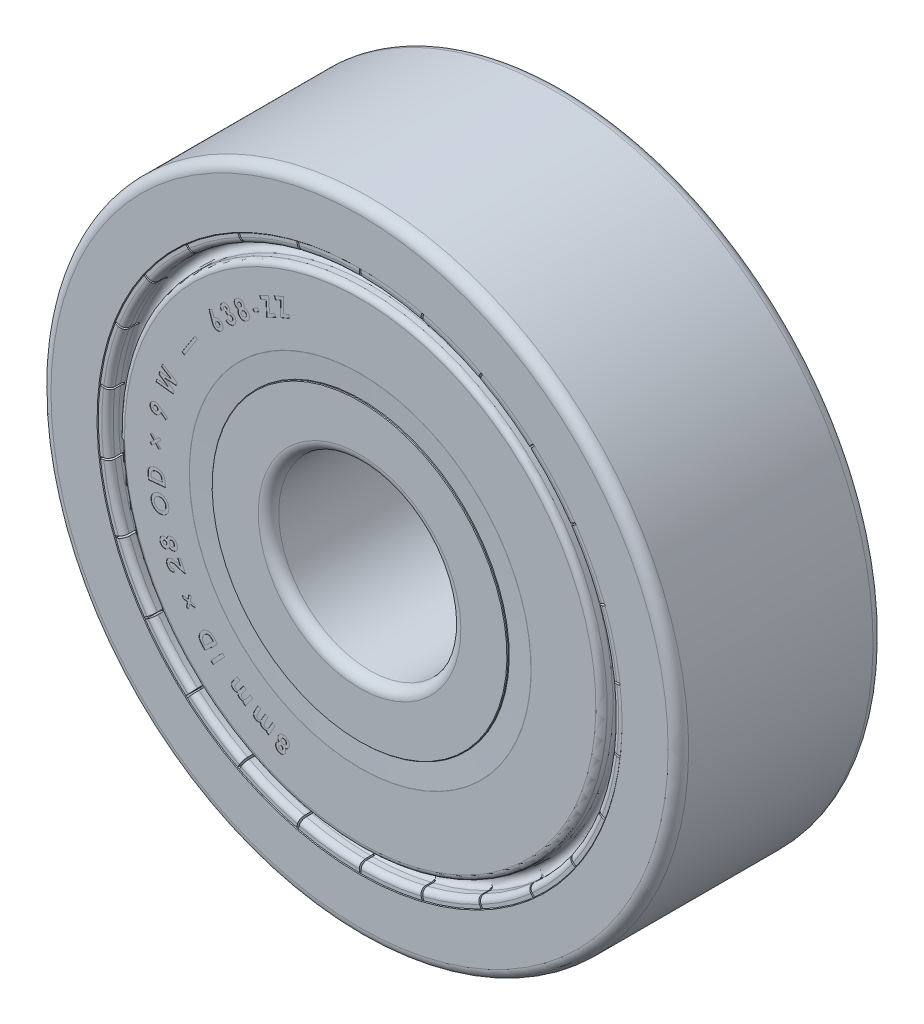
SolidWorks part; units mm, degrees
material "AISI 316 Annealed Stainless Steel Bar (SS)"
ref_plane "Front" through (0, 0, 0) normal (0, 0, 1) x (1, 0, 0)
ref_plane "Top" through (0, 0, 0) normal (0, 1, 0) x (1, 0, 0)
ref_plane "Right" through (0, 0, 0) normal (1, 0, 0) x (0, 0, -1)
sketch "LAYOUT R" plane through (0, 0, 0) normal (1, 0, 0) x (0, 0, -1)
  line L0 (-4.05, 4) -> (4.05, 4)
  line L1 (4.5, -14) -> (-4.5, -14) construction
  line L2 (4.5, -14) -> (4.5, 2.5781) construction
  line L3 (4.05, 14) -> (-4.05, 14)
  line L4 (-4.5, -14) -> (-4.5, 13.55) construction
  line L6 (2.6982, 0) -> (-2.6982, 0) construction
  line L7 (-4.472, 6.5) -> (4.472, 6.5)
  line L8 (-4.472, 11.5) -> (4.472, 11.5)
  line L11 (-8.89, 0) -> (8.89, 0) construction
  line L12 (-4.5, 13.55) -> (-4.5, 11.528)
  line L13 (4.5, 13.55) -> (4.5, 11.528)
  line L16 (-4.5, 6.472) -> (-4.5, 4.45)
  line L17 (4.5, 6.472) -> (4.5, 4.45)
  line L30 (-4.472, 11.5) -> (-4.472, 6.5) construction
  line L31 (4.472, 11.5) -> (4.472, 6.5) construction
  line L32 (-4.472, 7.5) -> (4.472, 7.5) construction
  line L33 (-4.4718, 7.5) -> (-4.4281, 6.5)
  line L34 (4.4718, 7.5) -> (4.4281, 6.5)
  line L35 (-4.472, 11.1) -> (4.472, 11.1) construction
  line L38 (-4.5, 11.528) -> (4.5, 11.528) construction
  line L39 (-4.472, 11.5) -> (-4.472, 11.35)
  line L40 (-4.222, 11.1) -> (-3.972, 11.1)
  line L41 (-4.472, 7.5109) -> (-4.472, 10.35)
  line L42 (-4.222, 10.6) -> (-3.972, 10.6)
  line L43 (4.472, 7.5109) -> (4.472, 10.35)
  line L44 (4.222, 10.6) -> (3.972, 10.6)
  line L45 (4.222, 11.1) -> (3.972, 11.1)
  line L46 (-4.472, 10.6) -> (4.472, 10.6) construction
  line L50 (-1.3199, 10.5) -> (1.3199, 10.5) construction
  line L53 (4.472, 6.5) -> (4.5, 6.472)
  line L54 (-4.472, 6.5) -> (-4.5, 6.472)
  line L56 (-4.5, 6.472) -> (4.5, 6.472) construction
  line L57 (4.5, 11.528) -> (4.472, 11.5) construction
  line L58 (4.5, 11.528) -> (4.472, 11.5)
  line L60 (-4.5, 11.528) -> (-4.472, 11.5) construction
  line L61 (-4.5, 11.528) -> (-4.472, 11.5)
  line L64 (-3.972, 10.6) -> (-3.972, 11.1) construction
  line L65 (3.972, 10.6) -> (3.972, 11.1) construction
  line L66 (4.472, 11.5) -> (4.472, 11.35)
  arc A2 (-4.222, 10.6) -> (-4.472, 10.35) centre (-4.222, 10.35) ccw
  arc A3 (4.472, 10.35) -> (4.222, 10.6) centre (4.222, 10.35) ccw
  arc A4 (4.4718, 7.5) -> (4.472, 7.5109) centre (4.222, 7.5109) ccw
  arc A5 (-4.472, 7.5109) -> (-4.4718, 7.5) centre (-4.222, 7.5109) ccw
  arc A6 (-3.972, 10.6) -> (-3.972, 11.1) centre (-3.972, 10.85) ccw
  arc A7 (3.972, 11.1) -> (3.972, 10.6) centre (3.972, 10.85) ccw
  arc A8 (-4.05, 14) -> (-4.5, 13.55) centre (-4.05, 13.55) ccw
  arc A9 (-4.5, 4.45) -> (-4.05, 4) centre (-4.05, 4.45) ccw
  arc A10 (4.05, 4) -> (4.5, 4.45) centre (4.05, 4.45) ccw
  arc A11 (-4.472, 11.35) -> (-4.222, 11.1) centre (-4.222, 11.35) ccw
  arc A12 (4.222, 11.1) -> (4.472, 11.35) centre (4.222, 11.35) ccw
  arc A13 (4.5, 13.55) -> (4.05, 14) centre (4.05, 13.55) ccw
  point P0 (0, 0)
  point P7 (-4.05, 14)
  point P8 (-4.222, 11.1)
  point P15 (0, 0)
  point P29 (-4.472, 11.35)
  point P38 (-4.4718, 7.5)
  point P54 (-4.472, 10.35)
  point P55 (-4.222, 10.6)
  point P56 (-4.472, 10.35)
  point P58 (-4.472, 7.5109)
  point P59 (-4.4718, 7.5)
  point P60 (4.222, 10.6)
  point P62 (4.472, 10.35)
  point P63 (4.472, 7.5109)
  point P64 (4.4718, 7.5)
  point P71 (-4.5, 13.55)
  point P72 (-4.5, 4.45)
  point P73 (-4.05, 4)
  point P74 (4.05, 4)
  point P75 (4.5, 4.45)
  point P80 (4.05, 14)
  point P81 (4.222, 11.1)
  point P88 (4.472, 11.35)
  point P91 (4.5, 13.55)
  dimension "D21" = 0.5
  dimension "D33" = 0.45
  dimension "D3" = 4
  dimension "D4" = 6.5
  dimension "D5" = 11.5
  dimension "D24" = 9
  dimension "D6" = 8.972
  dimension "D7" = 8.972
  dimension "D11" = 1
  dimension "D12" = 2.5
  dimension "D13" = 2.5
  dimension "D14" = 0.4
  dimension "D17" = 0.028
  dimension "D18" = 0.5
  dimension "D19" = 0.5
  dimension "D20" = 0.5
  dimension "D15" = 1
  dimension "D23" = 45
  dimension "D25" = 45
  dimension "D27" = 0.028
  dimension "D28" = 14
  dimension "D29" = 9
  dimension "D30" = 28
  dimension "D8" = 4.5
  dimension "D31" = 45
  dimension "D32" = 45
sketch "Sketch R, INNER BODY" plane through (0, 0, 0) normal (1, 0, 0) x (0, 0, -1)
  line L1 (-4.472, 6.5) -> (-4.5, 6.472) construction
  line L3 (-4.5, 6.472) -> (-4.5, 4.45) construction
  line L12 (-8.89, 0) -> (8.89, 0) construction
  line L13 (-8.89, 0) -> (8.89, 0) construction
  line L14 (-4.05, 4) -> (4.05, 4) construction
  line L15 (4.5, 6.472) -> (4.5, 4.45) construction
  line L16 (4.472, 6.5) -> (4.5, 6.472) construction
  line L17 (-4.472, 6.5) -> (4.472, 6.5) construction
  line L18 (-4.472, 6.5) -> (-4.5, 6.472)
  line L19 (-4.5, 6.472) -> (-4.5, 4.45)
  line L20 (-4.05, 4) -> (4.05, 4)
  line L21 (4.5, 6.472) -> (4.5, 4.45)
  line L22 (4.472, 6.5) -> (4.5, 6.472)
  line L23 (-4.472, 6.5) -> (4.472, 6.5)
  arc A0 (-4.5, 4.45) -> (-4.05, 4) centre (-4.05, 4.45) ccw construction
  arc A1 (4.05, 4) -> (4.5, 4.45) centre (4.05, 4.45) ccw construction
  arc A2 (-4.5, 4.45) -> (-4.05, 4) centre (-4.05, 4.45) ccw
  arc A3 (4.05, 4) -> (4.5, 4.45) centre (4.05, 4.45) ccw
sketch "Sketch R, OUTER BODY" plane through (0, 0, 0) normal (1, 0, 0) x (0, 0, -1)
  line L8 (-8.89, 0) -> (8.89, 0) construction
  line L9 (-8.89, 0) -> (8.89, 0) construction
  line L31 (-4.5, 13.55) -> (-4.5, 11.528) construction
  line L84 (-4.5, 11.528) -> (-4.472, 11.5) construction
  line L85 (-4.472, 11.5) -> (4.472, 11.5) construction
  line L86 (4.5, 11.528) -> (4.472, 11.5) construction
  line L87 (4.5, 13.55) -> (4.5, 11.528) construction
  line L88 (4.05, 14) -> (-4.05, 14) construction
  line L89 (-4.5, 13.55) -> (-4.5, 11.528)
  line L90 (-4.5, 11.528) -> (-4.472, 11.5)
  line L91 (-4.472, 11.5) -> (4.472, 11.5)
  line L92 (4.5, 11.528) -> (4.472, 11.5)
  line L93 (4.5, 13.55) -> (4.5, 11.528)
  line L94 (4.05, 14) -> (-4.05, 14)
  arc A6 (4.5, 13.55) -> (4.05, 14) centre (4.05, 13.55) ccw construction
  arc A7 (-4.05, 14) -> (-4.5, 13.55) centre (-4.05, 13.55) ccw construction
  arc A8 (4.5, 13.55) -> (4.05, 14) centre (4.05, 13.55) ccw
  arc A9 (-4.05, 14) -> (-4.5, 13.55) centre (-4.05, 13.55) ccw
sketch "Sketch R, SHIELD FACES" plane through (0, 0, 0) normal (1, 0, 0) x (0, 0, -1)
  line L0 (-8.89, 0) -> (8.89, 0) construction
  line L1 (-8.89, 0) -> (8.89, 0) construction
  line L29 (-4.472, 11.5) -> (-4.472, 11.35) construction
  line L32 (-4.222, 11.1) -> (-3.972, 11.1) construction
  line L34 (-4.222, 10.6) -> (-3.972, 10.6) construction
  line L36 (-4.472, 7.5109) -> (-4.472, 10.35) construction
  line L38 (-4.4718, 7.5) -> (-4.4281, 6.5) construction
  line L39 (-4.472, 6.5) -> (4.472, 6.5) construction
  line L40 (4.4718, 7.5) -> (4.4281, 6.5) construction
  line L43 (4.472, 7.5109) -> (4.472, 10.35) construction
  line L79 (4.222, 10.6) -> (3.972, 10.6) construction
  line L80 (4.222, 11.1) -> (3.972, 11.1) construction
  line L81 (4.472, 11.5) -> (4.472, 11.35) construction
  line L82 (-4.472, 11.5) -> (4.472, 11.5) construction
  line L83 (-4.472, 11.5) -> (-4.472, 11.35)
  line L84 (-4.222, 11.1) -> (-3.972, 11.1)
  line L85 (-4.222, 10.6) -> (-3.972, 10.6)
  line L86 (-4.472, 7.5109) -> (-4.472, 10.35)
  line L87 (-4.4718, 7.5) -> (-4.4281, 6.5)
  line L88 (-4.4281, 6.5) -> (4.4281, 6.5)
  line L89 (4.4718, 7.5) -> (4.4281, 6.5)
  line L90 (4.472, 7.5109) -> (4.472, 10.35)
  line L91 (4.222, 10.6) -> (3.972, 10.6)
  line L92 (4.222, 11.1) -> (3.972, 11.1)
  line L93 (4.472, 11.5) -> (4.472, 11.35)
  line L94 (-4.472, 11.5) -> (4.472, 11.5)
  arc A28 (-4.472, 11.35) -> (-4.222, 11.1) centre (-4.222, 11.35) ccw construction
  arc A29 (-3.972, 10.6) -> (-3.972, 11.1) centre (-3.972, 10.85) ccw construction
  arc A30 (-4.222, 10.6) -> (-4.472, 10.35) centre (-4.222, 10.35) ccw construction
  arc A31 (4.472, 10.35) -> (4.222, 10.6) centre (4.222, 10.35) ccw construction
  arc A32 (3.972, 11.1) -> (3.972, 10.6) centre (3.972, 10.85) ccw construction
  arc A33 (4.222, 11.1) -> (4.472, 11.35) centre (4.222, 11.35) ccw construction
  arc A34 (-4.472, 11.35) -> (-4.222, 11.1) centre (-4.222, 11.35) ccw
  arc A35 (-3.972, 10.6) -> (-3.972, 11.1) centre (-3.972, 10.85) ccw
  arc A36 (-4.222, 10.6) -> (-4.472, 10.35) centre (-4.222, 10.35) ccw
  arc A37 (4.472, 10.35) -> (4.222, 10.6) centre (4.222, 10.35) ccw
  arc A38 (3.972, 11.1) -> (3.972, 10.6) centre (3.972, 10.85) ccw
  arc A39 (4.222, 11.1) -> (4.472, 11.35) centre (4.222, 11.35) ccw
  arc A40 (-4.472, 7.5109) -> (-4.4718, 7.5) centre (-4.222, 7.5109) ccw construction
  arc A41 (-4.472, 7.5109) -> (-4.4718, 7.5) centre (-4.222, 7.5109) ccw
  arc A42 (4.4718, 7.5) -> (4.472, 7.5109) centre (4.222, 7.5109) ccw construction
  arc A43 (4.4718, 7.5) -> (4.472, 7.5109) centre (4.222, 7.5109) ccw
revolve "Revolve INNER BODY" add sketch "Sketch R, INNER BODY" angle 360 about L13
revolve "Revolve OUTER BODY" add sketch "Sketch R, OUTER BODY" angle 360 about L9
revolve "Revolve SHIELDS" add sketch "Sketch R, SHIELD FACES" angle 360 about L1
sketch "Sketch TEXT RADIUS 1 — MANUALLY ASSIGN TEXT AND FONT SIZE (FROM EQUATIONS)" plane through (0, 0, 4.472) normal (0, 0, 1) x (1, 0, 0)
  circle A0 centre (0, 0) radius 8.625 construction
  text T0 "<b>8mm ID × 28 OD × 9 W  —  638-ZZ</b>" font "Century Gothic" height 0.75
  dimension "D1" = 17.25
extrude "Cut-Extrude LABEL 1" cut sketch "Sketch TEXT RADIUS 1 — MANUALLY ASSIGN TEXT AND FONT SIZE (FROM EQUATIONS)" against normal blind 0.0127
sketch "Sketch TEXT RADIUS 2 — MANUALLY ASSIGN TEXT AND FONT SIZE (FROM EQUATIONS)" plane through (0, 0, -4.472) normal (0, 0, -1) x (-1, 0, 0)
  circle A0 centre (0, 0) radius 8.625 construction
  text T0 "<b>8mm ID × 28 OD × 9 W  —  638-ZZ</b>" font "Century Gothic" height 0.75
  dimension "D1" = 17.25
extrude "Cut-Extrude LABEL 2" cut sketch "Sketch TEXT RADIUS 2 — MANUALLY ASSIGN TEXT AND FONT SIZE (FROM EQUATIONS)" against normal blind 0.0127
sketch "LAYOUT F, SLIT SEED" plane through (0, 0, 0) normal (0, 0, 1) x (1, 0, 0)
  line L0 (0, 0) -> (0, 12.7) construction
  line L3 (0.04, 11.4999) -> (0.04, 11.0447)
  line L4 (-0.04, 11.4999) -> (-0.04, 11.0447)
  circle A4 centre (0, 0) radius 11
  circle A5 centre (0, 0) radius 11.5
  circle A6 centre (0, 11) radius 0.06
  point P13 (-0.04, 11.4999)
  point P15 (0.04, 11.4999)
  dimension "D1" = 23
  dimension "D2" = 22
  dimension "D3" = 0.12
  dimension "D4" = 0.04
sketch "Sketch F, SLIT SEED" plane through (0, 0, 4.472) normal (0, 0, 1) x (1, 0, 0)
  line L1 (0.04, 11.4999) -> (0.04, 11.0447) construction
  line L8 (-0.04, 11.4999) -> (-0.04, 11.0447) construction
  line L9 (0.04, 11.4999) -> (0.04, 11.0447)
  line L10 (-0.04, 11.4999) -> (-0.04, 11.0447)
  circle A1 centre (0, 11) radius 0.06 construction
  circle A8 centre (0, 0) radius 11.5 construction
  arc A9 (-0.04, 11.0447) -> (0.04, 11.0447) centre (0, 11) ccw
  arc A10 (0.04, 11.4999) -> (-0.04, 11.4999) centre (0, 0) ccw
extrude "Cut-Extrude SLIT SEED F" cut sketch "Sketch F, SLIT SEED" along normal blind 0.635 from surface starting at face at (8.5196, 3.018, -4.472)
extrude "Cut-Extrude SLIT SEED B" cut sketch "Sketch F, SLIT SEED<2>" against normal blind 0.635
sketch "Sketch F, SLIT SEED<2>" plane through (0, 0, 4.472) normal (0, 0, 1) x (1, 0, 0) same geometry as "Sketch F, SLIT SEED"
pattern_circular "CirPattern1" count 26 over 360 of "Cut-Extrude SLIT SEED F"
pattern_circular "CirPattern2" count 26 over 360 of "Cut-Extrude SLIT SEED B" reverse direction yes
equation "\"_i__BORE\"= 8"
equation "\"_i__OUTSIDE_DIAMETER\" = 28"
equation "\"_i__WIDTH\"= 9"
equation "\"_user_applied_FONT_SIZE\"= int ( \"BODY_SPAN__SHIELD__OF_RADIUS\" * \"g_param__FONT_SIZE_RATIO\" * 100 ) / 100'MANUALLY ASSIGN TO FONT"
equation "\"BODY__HALF_WIDTH\"= \"_i__WIDTH\" / 2"
equation "\"BODY_SPAN___OF_DIAMETER\"= \"_i__OUTSIDE_DIAMETER\" - \"_i__BORE\""
equation "\"BODY_SPAN___OF_RADIUS\"= \"BODY_SPAN___OF_DIAMETER\" / 2"
equation "\"BODY_SPAN__BORE_AND_OD__OF RADIUS\"= ( \"BODY_SPAN___OF_RADIUS\" - \"BODY_SPAN__SHIELD__OF_RADIUS\" ) / 2"
equation "\"BODY_SPAN__SHIELD__OF_RADIUS\"= \"BODY_SPAN___OF_RADIUS\" * \"g_param__SHIELD_PANEL_SPAN__RATIO_OF_BODY_RADIAN\""
equation "\"BORE__RADIUS\"= \"_i__BORE\" / 2"
equation "\"CORNER_RADII\"= \"_i__WIDTH\" * \"g_param__CORNER_RADII__RATIO_TO_WIDTH\""
equation "\"OUTSIDE_RADIUS\"= \"_i__OUTSIDE_DIAMETER\" / 2"
equation "\"RING_INNER__OUTSIDE_RADIUS\"= \"BORE__RADIUS\" + \"BODY_SPAN__BORE_AND_OD__OF RADIUS\""
equation "\"RING_OUTER__INSIDE_DIAMETER\"= \"RING_OUTER__INSIDE_RADIUS\" * 2"
equation "\"RING_OUTER__INSIDE_RADIUS\"= ( \"_i__OUTSIDE_DIAMETER\" / 2 ) - \"BODY_SPAN__BORE_AND_OD__OF RADIUS\""
equation "\"SHIELD__BOTTOM_AND_TOP_REGIONS_SPAN\"= \"BODY_SPAN__SHIELD__OF_RADIUS\" * \"g_param__SHIELD__TOP_AND_BOTTOM_REGIONS_RATIO\""
equation "\"SHIELD__COMPRESSION_FILLET_DIAMETER\"= \"BODY_SPAN__SHIELD__OF_RADIUS\" * \"g_param__SHIELD_COMPRESSION_FILLET_DIAMETER_RATIO\""
equation "\"SHIELD__COMPRESSION_FILLET_RADIUS\"= \"SHIELD__COMPRESSION_FILLET_DIAMETER\" / 2"
equation "\"SHIELD__FACE_FILLET_DIAMETER\"= \"BODY_SPAN__SHIELD__OF_RADIUS\" * \"g_param__SHIELD_FACE_FILLET_RATIO\""
equation "\"SHIELD__FACE_INSET\"= \"SIDE_FACE_CHAMFERS\""
equation "\"SHIELD__FACE_TO_OPPOSING_BRG_BODY_FACE\"= \"_i__WIDTH\" - \"SHIELD__FACE_INSET\""
equation "\"SHIELD__HALF_SLIT_WIDTH\"= \"SHIELD__SLIT_WIDTH\" / 2"
equation "\"SHIELD__HALF_WALL\"= \"SHIELD__WALL\" / 2"
equation "\"SHIELD__SLIT_WIDTH\"= \"SHIELD__WALL\" / 5"
equation "\"SHIELD__WALL\"= \"BODY_SPAN__SHIELD__OF_RADIUS\" * \"g_param__SHIELD_WALL_TO_SPAN_RATIO\""
equation "\"SHIELD_SLIT__INSIDE_TERMINUS__DIAMETER\"= \"RING_OUTER__INSIDE_DIAMETER\" - \"SHIELD__BOTTOM_AND_TOP_REGIONS_SPAN\""
equation "\"SHIELD_SLIT__KEYHOLE_DIAMETER\"= \"SHIELD__SLIT_WIDTH\" * 1.5"
equation "\"SIDE_FACE_CHAMFERS\"= \"_i__OUTSIDE_DIAMETER\" * \"g_param__SIDE_CHAMFERS__RATIO_TO_OD\""
equation "\"TEXT_RADIUS\"= \"_i__BORE\" + ( \"BODY_SPAN___OF_DIAMETER\" / 2 ) - \"_user_applied_FONT_SIZE\""
equation "\"WIDTH__HALF\"= \"_i__WIDTH\" / 2"
equation "\"D1@CirPattern1\" = \"g_param__SHIELD__NUMBER_OF_SLITS\""
equation "\"D1@CirPattern2\" = \"g_param__SHIELD__NUMBER_OF_SLITS\""
equation "\"D1@LAYOUT F, SLIT SEED\"=\"RING_OUTER__INSIDE_DIAMETER\""
equation "\"D1@Sketch TEXT RADIUS 1 — MANUALLY ASSIGN TEXT AND FONT SIZE (FROM EQUATIONS)\" = \"TEXT_RADIUS\""
equation "\"D1@Sketch TEXT RADIUS 2 — MANUALLY ASSIGN TEXT AND FONT SIZE (FROM EQUATIONS)\" = \"TEXT_RADIUS\""
equation "\"D11@LAYOUT R\"=\"SHIELD__BOTTOM_AND_TOP_REGIONS_SPAN\""
equation "\"D12@LAYOUT R\" = \"g_param__SHIELD__INSIDE_BEVEL_ANGLE__DEGREES\""
equation "\"D13@LAYOUT R\"= \"g_param__SHIELD__INSIDE_BEVEL_ANGLE__DEGREES\""
equation "\"D14@LAYOUT R\"=\"SHIELD__WALL\""
equation "\"D15@LAYOUT R\"=\"SHIELD__BOTTOM_AND_TOP_REGIONS_SPAN\""
equation "\"D17@LAYOUT R\"=\"SIDE_FACE_CHAMFERS\""
equation "\"D18@LAYOUT R\"=\"SHIELD__COMPRESSION_FILLET_DIAMETER\""
equation "\"D19@LAYOUT R\"=\"SHIELD__COMPRESSION_FILLET_DIAMETER\""
equation "\"D2@LAYOUT F, SLIT SEED\"=\"SHIELD_SLIT__INSIDE_TERMINUS__DIAMETER\""
equation "\"D20@LAYOUT R\"=\"SHIELD__COMPRESSION_FILLET_DIAMETER\""
equation "\"D21@LAYOUT R\"=\"SHIELD__FACE_FILLET_DIAMETER\""
equation "\"D24@LAYOUT R\"=\"_i__WIDTH\""
equation "\"D27@LAYOUT R\"=\"SIDE_FACE_CHAMFERS\""
equation "\"D28@LAYOUT R\"=\"OUTSIDE_RADIUS\""
equation "\"D3@LAYOUT F, SLIT SEED\"=\"SHIELD_SLIT__KEYHOLE_DIAMETER\""
equation "\"D3@LAYOUT R\"=\"BORE__RADIUS\""
equation "\"D30@LAYOUT R\"=\"_i__OUTSIDE_DIAMETER\""
equation "\"D33@LAYOUT R\"=\"CORNER_RADII\""
equation "\"D4@LAYOUT F, SLIT SEED\"=\"SHIELD__HALF_SLIT_WIDTH\""
equation "\"D4@LAYOUT R\"=\"RING_INNER__OUTSIDE_RADIUS\""
equation "\"D5@LAYOUT F, SLIT SEED\"=\"SHIELD__HALF_SLIT_WIDTH\""
equation "\"D5@LAYOUT R\"=\"RING_OUTER__INSIDE_RADIUS\""
equation "\"D6@LAYOUT R\"=\"SHIELD__FACE_TO_OPPOSING_BRG_BODY_FACE\""
equation "\"D7@LAYOUT R\"=\"SHIELD__FACE_TO_OPPOSING_BRG_BODY_FACE\""
equation "\"D8@LAYOUT R\"=\"WIDTH__HALF\""
equation "\"g_param__CORNER_RADII__RATIO_TO_WIDTH\"= 0.05'ISO MAX IS 0.07 WHERE WIDTH IS LESS THAN DIAMETER"
equation "\"g_param__FONT_SIZE_RATIO\"= 0.15'EXPRESSES RADIAL PROPORTION OF SHIELD FACE"
equation "\"g_param__INDICIA__EXTRUSION_DEPTH\"=0.013'CONCAVE-EMBOSSED INDICIA ON SHIELD FACES"
equation "\"g_param__SHIELD__INSIDE_BEVEL_ANGLE__DEGREES\"= 2.5'SHOULD BE GREATER THAN 0 AND LESS THAN OR EQUAL TO 10, ORIGINALLY 1"
equation "\"g_param__SHIELD__NUMBER_OF_SLITS\"=26'OPTIONAL NUMBER OF SHIELD COMPRESSION RING SLITS"
equation "\"g_param__SHIELD__TOP_AND_BOTTOM_REGIONS_RATIO\"=0.2'PART OF RADIAL SHIELD SPAN OCCUPIED BY INMOST BEVEL, ORIGINALLY 0.2"
equation "\"g_param__SHIELD_COMPRESSION_FILLET_DIAMETER_RATIO\"=0.1'ORIGINALLY 0,1"
equation "\"g_param__SHIELD_FACE_FILLET_RATIO\"=0.1'ORIGINALLY 0.1"
equation "\"g_param__SHIELD_FACE_INSET__RATIO_OF_WIDTH\"= 0.035'ISO-UNSPECIFIED, SHOULD BE AT LEAST 0.025 and LESS THAN 0.036"
equation "\"g_param__SHIELD_PANEL_SPAN__RATIO_OF_BODY_RADIAN\"= 0.5'ISO-UNSPECIFIED, ORIGINALLY 0.5"
equation "\"g_param__SHIELD_WALL_TO_SPAN_RATIO\"=0.08'SHOULD BE LESS THAN 0.015, ORIGINALLY 0.08, PRESCRIBES MATERIAL THICKNESS"
equation "\"g_param__SIDE_CHAMFERS__RATIO_TO_OD\"= 0.001'NOT ISO-SPECIFIED"
